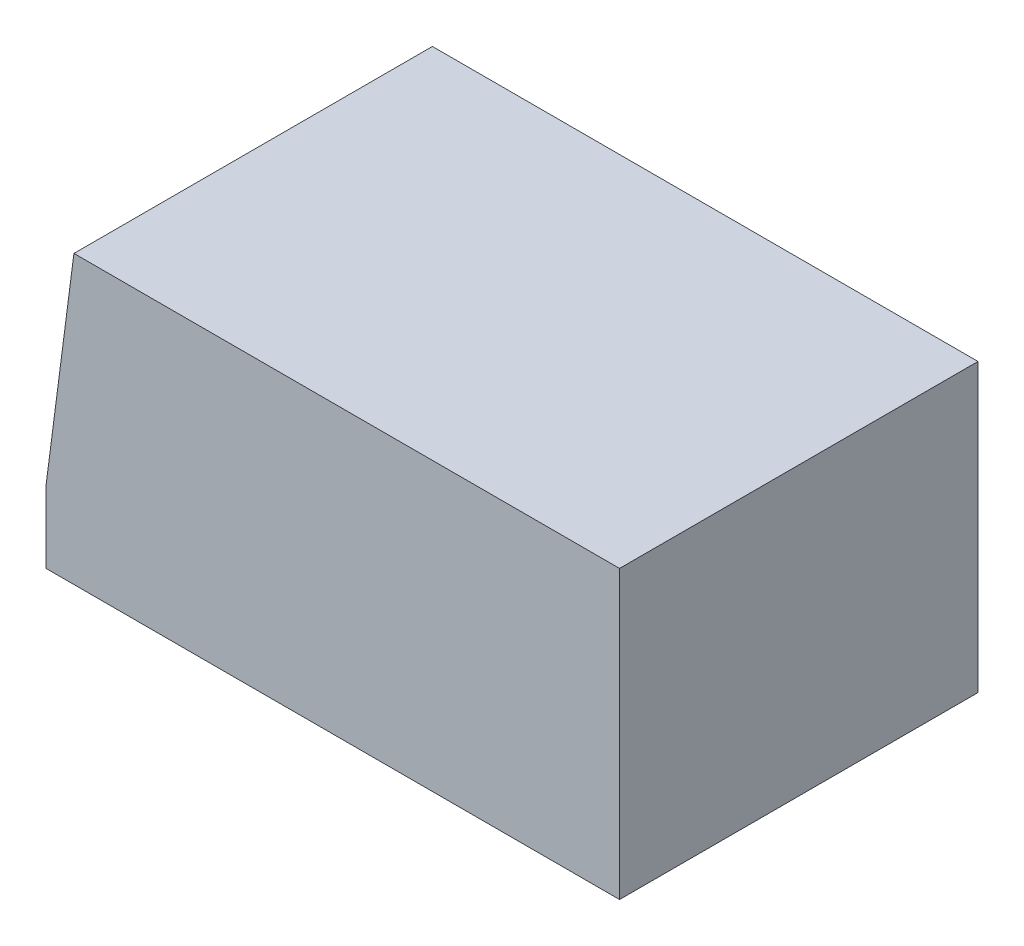
SolidWorks part; units mm, degrees
ref_plane "Plan de face" through (0, 0, 0) normal (0, 0, 1) x (1, 0, 0)
ref_plane "Plan de dessus" through (0, 0, 0) normal (0, 1, 0) x (1, 0, 0)
ref_plane "Plan de droite" through (0, 0, 0) normal (1, 0, 0) x (0, 0, -1)
sketch "Esquisse1" plane through (0, 0, 0) normal (0, 1, 0) x (1, 0, 0)
  line L1 (-40, -25) -> (40, -25)
  line L2 (-40, -25) -> (-40, 25)
  line L3 (-40, 25) -> (40, 25)
  line L4 (40, -25) -> (40, 25)
  line L5 (-40, -25) -> (40, 25) construction
  line L6 (-40, 25) -> (40, -25) construction
  point P0 (0, 0)
  dimension "D1" = 50
  dimension "D2" = 80
extrude "Boss.-Extru.1" add sketch "Esquisse1" along normal blind 40
chamfer "Chanfrein1" distance 30 angle 7.4 1 edges at (-40, 40, 0) first distance on face at (-40, 20, 0)
sketch "Esquisse2" plane through (-40.6137, 5.2748, 0) normal (-0.9917, 0.1288, 0) x (0, 0, 1)
  line L0 (25, 18.821) -> (-25, 18.821) construction
  line L3 (25, 35.0169) -> (25, 4.7649) construction
  line L4 (-25, 4.7649) -> (-25, 35.0169) construction
  circle A0 centre (0, 18.821) radius 12.5
  dimension "D1" = 25
extrude "Enlèv. mat.-Extru.1" cut sketch "Esquisse2" against normal blind 40
